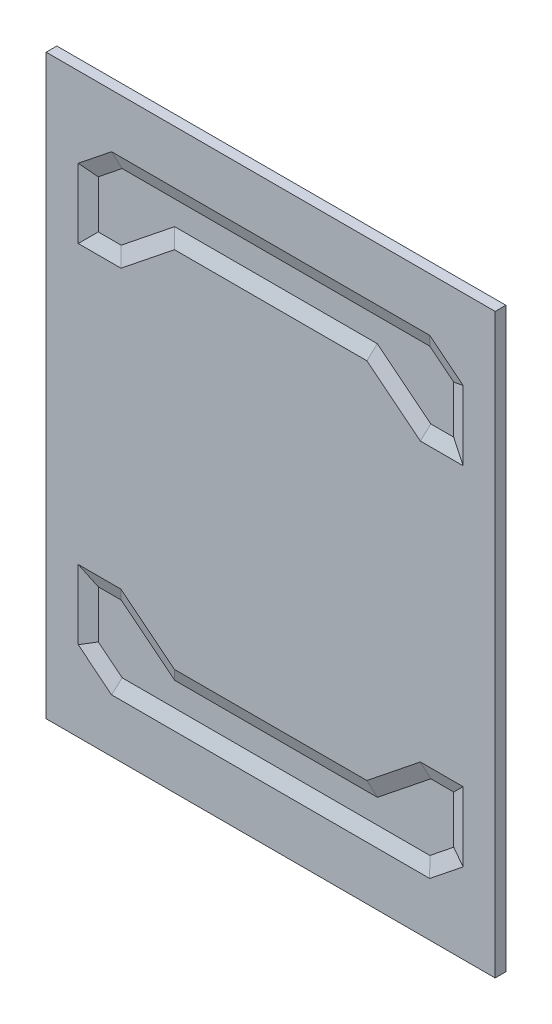
SolidWorks part; units mm, degrees
ref_plane "Plan de face" through (0, 0, 0) normal (0, 0, 1) x (1, 0, 0)
ref_plane "Plan de dessus" through (0, 0, 0) normal (0, 1, 0) x (1, 0, 0)
ref_plane "Plan de droite" through (0, 0, 0) normal (1, 0, 0) x (0, 0, -1)
sketch "Esquisse1" plane through (0, 0, 0) normal (0, 0, 1) x (1, 0, 0)
  line L1 (0, 0) -> (420, 0)
  line L2 (0, 0) -> (0, 540)
  line L3 (0, 540) -> (420, 540)
  line L4 (420, 0) -> (420, 540)
  dimension "D1" = 420
  dimension "D2" = 540
extrude "Boss.-Extru.1" add sketch "Esquisse1" along normal blind 10
sketch "Esquisse2" plane through (0, 0, 10) normal (0, 0, 1) x (1, 0, 0)
  line L0 (210, 540) -> (210, 0) construction
  line L1 (420, 540) -> (0, 540) construction
  line L2 (0, 0) -> (420, 0) construction
  line L3 (300, 460) -> (120, 460) construction
  line L4 (120, 460) -> (70, 500) construction
  line L5 (70, 500) -> (30, 500) construction
  line L6 (30, 500) -> (30, 435) construction
  line L7 (30, 435) -> (61.25, 410) construction
  line L8 (61.25, 410) -> (358.75, 410) construction
  line L9 (0, 540) -> (0, 0) construction
  line L10 (61.25, 410) -> (61.25, 435) construction
  line L11 (61.25, 435) -> (20.8816, 435) construction
  line L12 (120, 460) -> (70, 460) construction
  line L13 (70, 500) -> (70, 460) construction
  line L14 (300, 460) -> (350, 500) construction
  line L15 (350, 500) -> (390, 500) construction
  line L16 (390, 500) -> (390, 435) construction
  line L17 (390, 435) -> (358.75, 410) construction
  line L18 (300, 340) -> (120, 340) construction
  line L19 (61.25, 290) -> (358.75, 290) construction
  line L20 (300, 340) -> (350, 380) construction
  line L21 (350, 380) -> (390, 380) construction
  line L22 (390, 380) -> (390, 315) construction
  line L23 (390, 315) -> (358.75, 290) construction
  line L24 (120, 340) -> (70, 380) construction
  line L25 (70, 380) -> (30, 380) construction
  line L26 (30, 380) -> (30, 315) construction
  line L27 (30, 315) -> (61.25, 290) construction
  line L28 (300, 220) -> (120, 220) construction
  line L29 (61.25, 170) -> (358.75, 170) construction
  line L30 (300, 220) -> (350, 260) construction
  line L31 (350, 260) -> (390, 260) construction
  line L32 (390, 260) -> (390, 195) construction
  line L33 (390, 195) -> (358.75, 170) construction
  line L34 (120, 220) -> (70, 260) construction
  line L35 (70, 260) -> (30, 260) construction
  line L36 (30, 260) -> (30, 195) construction
  line L37 (30, 195) -> (61.25, 170) construction
  line L38 (300, 100) -> (120, 100)
  line L39 (61.25, 50) -> (358.75, 50)
  line L40 (300, 100) -> (350, 140)
  line L41 (350, 140) -> (390, 140)
  line L42 (390, 140) -> (390, 75)
  line L43 (390, 75) -> (358.75, 50)
  line L44 (120, 100) -> (70, 140)
  line L45 (70, 140) -> (30, 140)
  line L46 (30, 140) -> (30, 75)
  line L47 (30, 75) -> (61.25, 50)
  line L48 (420, 0) -> (420, 540) construction
  line L49 (0, 270) -> (420, 270) construction
  line L50 (30, 465) -> (61.25, 490)
  line L51 (30, 400) -> (30, 465)
  line L52 (70, 400) -> (30, 400)
  line L53 (120, 440) -> (70, 400)
  line L54 (390, 465) -> (358.75, 490)
  line L55 (390, 400) -> (390, 465)
  line L56 (350, 400) -> (390, 400)
  line L57 (300, 440) -> (350, 400)
  line L58 (61.25, 490) -> (358.75, 490)
  line L59 (300, 440) -> (120, 440)
  point P19 (210, 460)
  point P23 (210, 410)
  dimension "D1" = 40
  dimension "D2" = 40
  dimension "D3" = 50
  dimension "D4" = 30
  dimension "D5" = 50
  dimension "D6" = 25
  dimension "D7" = 40
  dimension "D9" = 410
  dimension "D10" = 30
  dimension "D8" = 4
extrude "Enlèv. mat.-Extru.1" cut sketch "Esquisse2" against normal blind 5
chamfer "Chanfrein1" distance 5 angle 70 20 edges at (390, 107.5, 5) (374.375, 62.5, 5) (210, 50, 5) (45.625, 62.5, 5) (30, 107.5, 5) (50, 140, 5) (95, 120, 5) (210, 100, 5) (325, 120, 5) (370, 140, 5) (45.625, 477.5, 5) (210, 490, 5) (374.375, 477.5, 5) (390, 432.5, 5) (370, 400, 5) (325, 420, 5) (210, 440, 5) (95, 420, 5) (50, 400, 5) (30, 432.5, 5) first distance on face at (390, 107.5, 7.5) first distance on face at (374.375, 62.5, 7.5) first distance on face at (210, 50, 7.5) first distance on face at (45.625, 62.5, 7.5) first distance on face at (30, 107.5, 7.5) first distance on face at (50, 140, 7.5) first distance on face at (95, 120, 7.5) first distance on face at (210, 100, 7.5) first distance on face at (325, 120, 7.5) first distance on face at (370, 140, 7.5) first distance on face at (45.625, 477.5, 7.5) first distance on face at (210, 490, 7.5) first distance on face at (374.375, 477.5, 7.5) first distance on face at (390, 432.5, 7.5) first distance on face at (370, 400, 7.5) first distance on face at (325, 420, 7.5) first distance on face at (210, 440, 7.5) first distance on face at (95, 420, 7.5) first distance on face at (50, 400, 7.5) first distance on face at (30, 432.5, 7.5)
